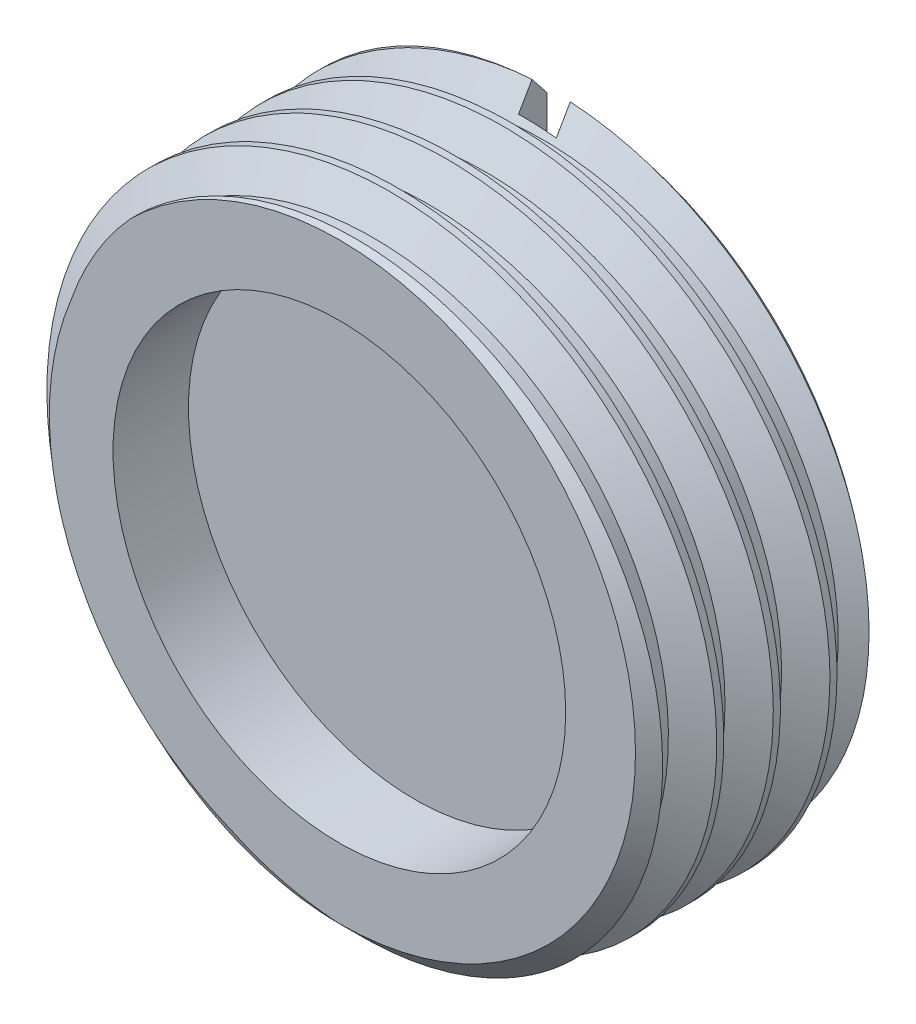
SolidWorks part; units mm, degrees
material "Alliage de zinc AC41A, brut"
ref_plane "Plan de face" through (0, 0, 0) normal (0, 0, 1) x (1, 0, 0)
ref_plane "Plan de dessus" through (0, 0, 0) normal (0, 1, 0) x (1, 0, 0)
ref_plane "Plan de droite" through (0, 0, 0) normal (1, 0, 0) x (0, 0, -1)
sketch "Esquisse1" plane through (0, 0, 0) normal (0, 0, 1) x (1, 0, 0)
  circle A0 centre (0, 0) radius 8.5
  dimension "D1" = 17
extrude "Boss.-Extru.1" add sketch "Esquisse1" along normal blind 6
thread "Filetage1" pitch 1.5 method cut profile "Profil de filetage1" start angle 0, offset 1.5, length 7.5, pitch 1.5, diameter 17
ref_plane "Plan1" through (8.5, 0, -1.5) normal (0, -1, 0) x (1, 0, 0)
sketch "Profil de filetage1" plane through (8.5, 0, -1.5) normal (0, -1, 0) x (1, 0, 0)
  line L0 (0, 0) -> (0, 1.5) construction
  line L11 (0, 0) -> (0, 1.3125)
  line L12 (0, 1.3125) -> (-0.8119, 0.8437)
  line L13 (-0.8119, 0.8437) -> (-0.8119, 0.4687)
  line L15 (-0.8119, 0.4687) -> (0, 0)
  line L17 (-0.8119, 0.6562) -> (0, 0.6562) construction
  point P2 (0, 0)
  dimension "Pitch" = 1.5
  dimension "Profile_Angle" = 60
  dimension "Profile_Land" = 0.375
  dimension "Profile_Height" = 0.8119
sketch "Esquisse4" plane through (0, 0, 6) normal (0, 0, 1) x (1, 0, 0)
  circle A0 centre (0, 0) radius 6
  dimension "D1" = 12
extrude "Enlèv. mat.-Extru.1" cut sketch "Esquisse4" against normal blind 2
sketch "Esquisse5" plane through (0, 0, 0) normal (0, 0, -1) x (-1, 0, 0)
  line L1 (-0.5, -8.5) -> (0.5, -8.5)
  line L2 (-0.5, -8.5) -> (-0.5, 8.5)
  line L3 (-0.5, 8.5) -> (0.5, 8.5)
  line L4 (0.5, -8.5) -> (0.5, 8.5)
  point P4 (0.5, 0)
  point P6 (0, 8.5)
  dimension "D1" = 17
  dimension "D2" = 1
extrude "Enlèv. mat.-Extru.2" cut sketch "Esquisse5" against normal blind 0.75
sketch "Esquisse6" plane through (0, 0, 0) normal (0, 1, 0) x (1, 0, 0)
  line L0 (-8, 0) -> (-8.5, -0.4)
  line L1 (8.5, -6) -> (-8.5, -6) construction
  line L2 (8.5, -6) -> (8.5, 0) construction
  line L3 (8.5, 0) -> (-8.5, 0) construction
  line L4 (-8.5, -6) -> (-8.5, 0) construction
  line L5 (-8.5, -5.35) -> (-7.85, -6)
  line L6 (-8.5, -0.4) -> (-8.5, 0)
  line L7 (-8.5, 0) -> (-8, 0)
  line L8 (-8.5, -5.35) -> (-8.5, -6)
  line L9 (-8.5, -6) -> (-7.85, -6)
  line L10 (0, 0) -> (0, -6) construction
  point P4 (0, 0)
  dimension "D1" = 17
  dimension "D2" = 6
  dimension "D3" = 0.5
  dimension "D4" = 0.4
  dimension "D5" = 0.65
  dimension "D6" = 0.65
revolve "Enlèvement de matière-Révolution1" cut sketch "Esquisse6" angle 360 about L10
